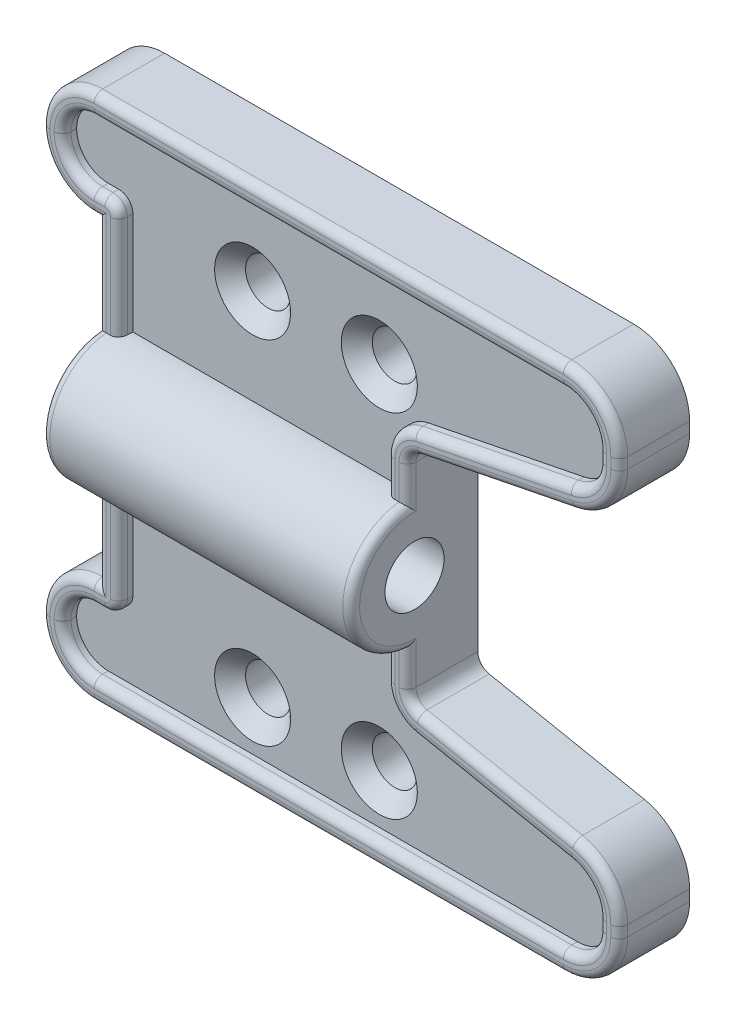
SolidWorks part; units mm, degrees
ref_plane "Спереди" through (0, 0, 0) normal (0, 0, 1) x (1, 0, 0)
ref_plane "Сверху" through (0, 0, 0) normal (0, 1, 0) x (1, 0, 0)
ref_plane "Справа" through (0, 0, 0) normal (1, 0, 0) x (0, 0, -1)
sketch "Эскиз1" plane through (0, 0, 0) normal (0, 0, 1) x (1, 0, 0)
  line L0 (0, -22.5) -> (0, 22.5)
  line L1 (0, 22.5) -> (-0.51, 22.5)
  line L2 (-8, 29.99) -> (-8, 30.01)
  line L3 (-0.51, 37.5) -> (66.133, 37.5)
  line L4 (74.083, 29.55) -> (74.083, 28.021)
  line L5 (67.688, 20.2245) -> (45.6088, 15.8209)
  line L6 (44, 13.8595) -> (44, -13.8595)
  line L7 (45.6088, -15.8209) -> (67.688, -20.2245)
  line L8 (74.083, -28.021) -> (74.083, -29.55)
  line L9 (66.133, -37.5) -> (-0.51, -37.5)
  line L10 (-8, -30.01) -> (-8, -29.99)
  line L11 (-0.51, -22.5) -> (0, -22.5)
  arc A0 (-8, -30.01) -> (-0.51, -37.5) centre (-0.51, -30.01) ccw
  arc A1 (-8, -29.99) -> (-0.51, -22.5) centre (-0.51, -29.99) cw
  arc A2 (-0.51, 22.5) -> (-8, 29.99) centre (-0.51, 29.99) cw
  arc A3 (-8, 30.01) -> (-0.51, 37.5) centre (-0.51, 30.01) cw
  arc A4 (66.133, -37.5) -> (74.083, -29.55) centre (66.133, -29.55) ccw
  arc A5 (74.083, -28.021) -> (67.688, -20.2245) centre (66.133, -28.021) ccw
  arc A6 (67.688, 20.2245) -> (74.083, 28.021) centre (66.133, 28.021) ccw
  arc A7 (74.083, 29.55) -> (66.133, 37.5) centre (66.133, 29.55) ccw
  arc A8 (45.6088, -15.8209) -> (44, -13.8595) centre (46, -13.8595) cw
  arc A9 (44, 13.8595) -> (45.6088, 15.8209) centre (46, 13.8595) cw
  circle A10 centre (20, 22.5) radius 3.2
  circle A11 centre (38, 22.5) radius 3.2
  circle A12 centre (20, -27.5) radius 3.2
  circle A13 centre (38, -27.5) radius 3.2
  point P15 (-8, -37.5)
  point P18 (-8, -22.5)
  point P21 (-8, 22.5)
  point P24 (-8, 37.5)
  point P27 (74.083, -37.5)
  point P30 (74.083, -21.5)
  point P33 (74.083, 21.5)
  point P36 (74.083, 37.5)
  point P39 (44, -15.5)
  point P42 (44, 15.5)
  dimension "D6" = 7.49
  dimension "D11" = 7.95
  dimension "D12" = 2
  dimension "D13" = 6.4
  dimension "D1" = 45
  dimension "D2" = 22.5
  dimension "D3" = 15
  dimension "D4" = 8
  dimension "D5" = 15
  dimension "D7" = 31
  dimension "D8" = 16
  dimension "D9" = 16
  dimension "D10" = 44
  dimension "D14" = 20
  dimension "D15" = 18
  dimension "D16" = 50
  dimension "D17" = 10
extrude "Бобышка-Вытянуть1" add sketch "Эскиз1" along normal blind 8
sketch "Эскиз2" plane through (0, 0, 8) normal (0, 0, 1) x (1, 0, 0)
  line L0 (0, -22.5) -> (0, 22.5)
  line L1 (0, 22.5) -> (-0.51, 22.5)
  line L2 (-8, 29.99) -> (-8, 30.01)
  line L3 (-0.51, 37.5) -> (66.133, 37.5)
  line L4 (74.083, 29.55) -> (74.083, 28.021)
  line L5 (67.688, 20.2245) -> (45.6088, 15.8209)
  line L6 (44, 13.8595) -> (44, -13.8595)
  line L7 (45.6088, -15.8209) -> (67.688, -20.2245)
  line L8 (74.083, -28.021) -> (74.083, -29.55)
  line L9 (66.133, -37.5) -> (-0.51, -37.5)
  line L10 (-8, -30.01) -> (-8, -29.99)
  line L11 (-0.51, -22.5) -> (0, -22.5)
  line L12 (3, -25.5) -> (3, 25.5)
  line L13 (3, 25.5) -> (-0.51, 25.5)
  line L14 (-5, 29.99) -> (-5, 30.01)
  line L15 (-0.51, 34.5) -> (66.133, 34.5)
  line L16 (71.083, 29.55) -> (71.083, 28.021)
  line L17 (67.1012, 23.1666) -> (45.022, 18.7629)
  line L18 (41, 13.8595) -> (41, -13.8595)
  line L19 (45.022, -18.7629) -> (67.1012, -23.1666)
  line L20 (71.083, -28.021) -> (71.083, -29.55)
  line L21 (66.133, -34.5) -> (-0.51, -34.5)
  line L22 (-5, -30.01) -> (-5, -29.99)
  line L23 (-0.51, -25.5) -> (3, -25.5)
  arc A0 (-8, -30.01) -> (-0.51, -37.5) centre (-0.51, -30.01) ccw
  arc A1 (-8, -29.99) -> (-0.51, -22.5) centre (-0.51, -29.99) cw
  arc A2 (-0.51, 22.5) -> (-8, 29.99) centre (-0.51, 29.99) cw
  arc A3 (-8, 30.01) -> (-0.51, 37.5) centre (-0.51, 30.01) cw
  arc A4 (66.133, -37.5) -> (74.083, -29.55) centre (66.133, -29.55) ccw
  arc A5 (74.083, -28.021) -> (67.688, -20.2245) centre (66.133, -28.021) ccw
  arc A6 (67.688, 20.2245) -> (74.083, 28.021) centre (66.133, 28.021) ccw
  arc A7 (74.083, 29.55) -> (66.133, 37.5) centre (66.133, 29.55) ccw
  arc A8 (45.6088, -15.8209) -> (44, -13.8595) centre (46, -13.8595) cw
  arc A9 (44, 13.8595) -> (45.6088, 15.8209) centre (46, 13.8595) cw
  arc A10 (-0.51, 25.5) -> (-5, 29.99) centre (-0.51, 29.99) cw
  arc A11 (-5, 30.01) -> (-0.51, 34.5) centre (-0.51, 30.01) cw
  arc A12 (71.083, 29.55) -> (66.133, 34.5) centre (66.133, 29.55) ccw
  arc A13 (67.1012, 23.1666) -> (71.083, 28.021) centre (66.133, 28.021) ccw
  arc A14 (41, 13.8595) -> (45.022, 18.7629) centre (46, 13.8595) cw
  arc A15 (45.022, -18.7629) -> (41, -13.8595) centre (46, -13.8595) cw
  arc A16 (71.083, -28.021) -> (67.1012, -23.1666) centre (66.133, -28.021) ccw
  arc A17 (66.133, -34.5) -> (71.083, -29.55) centre (66.133, -29.55) ccw
  arc A18 (-5, -30.01) -> (-0.51, -34.5) centre (-0.51, -30.01) ccw
  arc A19 (-5, -29.99) -> (-0.51, -25.5) centre (-0.51, -29.99) cw
  dimension "D2" = 7.49
  dimension "D4" = 7.95
  dimension "D5" = 3
  dimension "D1" = 45
  dimension "D3" = 44
extrude "Бобышка-Вытянуть2" add sketch "Эскиз2" along normal blind 2
fillet "Скругление1" radius 2 2 edges at (3, 25.5, 9) (3, -25.5, 9)
fillet "Скругление4" radius 1.2 24 edges at (2.4142, -24.9142, 10) (0.245, -25.5, 10) (-3.6849, -26.8151, 10) (-5, -30, 10) (-3.6849, -33.1849, 10) (32.8115, -34.5, 10) (69.6332, -33.0502, 10) (71.083, -28.7855, 10) (69.9602, -24.8817, 10) (56.0616, -20.9648, 10) (42.1341, -17.0305, 10) (41, 0, 10) (42.1341, 17.0305, 10) (56.0616, 20.9648, 10) (69.9602, 24.8817, 10) (71.083, 28.7855, 10) (69.6332, 33.0502, 10) (32.8115, 34.5, 10) (-3.6849, 33.1849, 10) (-5, 30, 10) (-3.6849, 26.8151, 10) (0.245, 25.5, 10) (2.4142, 24.9142, 10) (3, 0, 10)
fillet "Скругление5" radius 1.2 22 edges at (-0.255, -22.5, 10) (-5.8062, -24.6938, 10) (-8, -30, 10) (-5.8062, -35.3062, 10) (32.8115, -37.5, 10) (71.7545, -35.1715, 10) (74.083, -28.7855, 10) (72.2798, -22.9791, 10) (56.6484, -18.0227, 10) (44.4537, -15.1279, 10) (44, 0, 10) (44.4537, 15.1279, 10) (56.6484, 18.0227, 10) (72.2798, 22.9791, 10) (74.083, 28.7855, 10) (71.7545, 35.1715, 10) (-0.255, 22.5, 10) (-5.8062, 24.6938, 10) (-8, 30, 10) (-5.8062, 35.3062, 10) (0, 0, 10) (32.8115, 37.5, 10)
chamfer "Фаска1" distance 2.2 angle 45 4 edges at (41.2, -27.5, 8) (23.2, -27.5, 8) (41.2, 22.5, 8) (23.2, 22.5, 8)
sketch "Эскиз3" plane through (0, 0, 0) normal (-1, 0, 0) x (0, 0, 1)
  circle A0 centre (9, 0) radius 9
  dimension "D1" = 18
extrude "Бобышка-Вытянуть3" add sketch "Эскиз3" against normal blind 44
sketch "Эскиз4" plane through (0, 0, 0) normal (-1, 0, 0) x (0, 0, 1)
  circle A0 centre (9, 0) radius 4.2
  arc A1 (8.8, -8.9978) -> (8.8, 8.9978) centre (9, 0) ccw construction
  dimension "D1" = 8.4
extrude "Вырез-Вытянуть1" cut sketch "Эскиз4" against normal through all
fillet "Скругление6" radius 1.2 2 edges at (0, 0, 18) (44, 0, 18)
